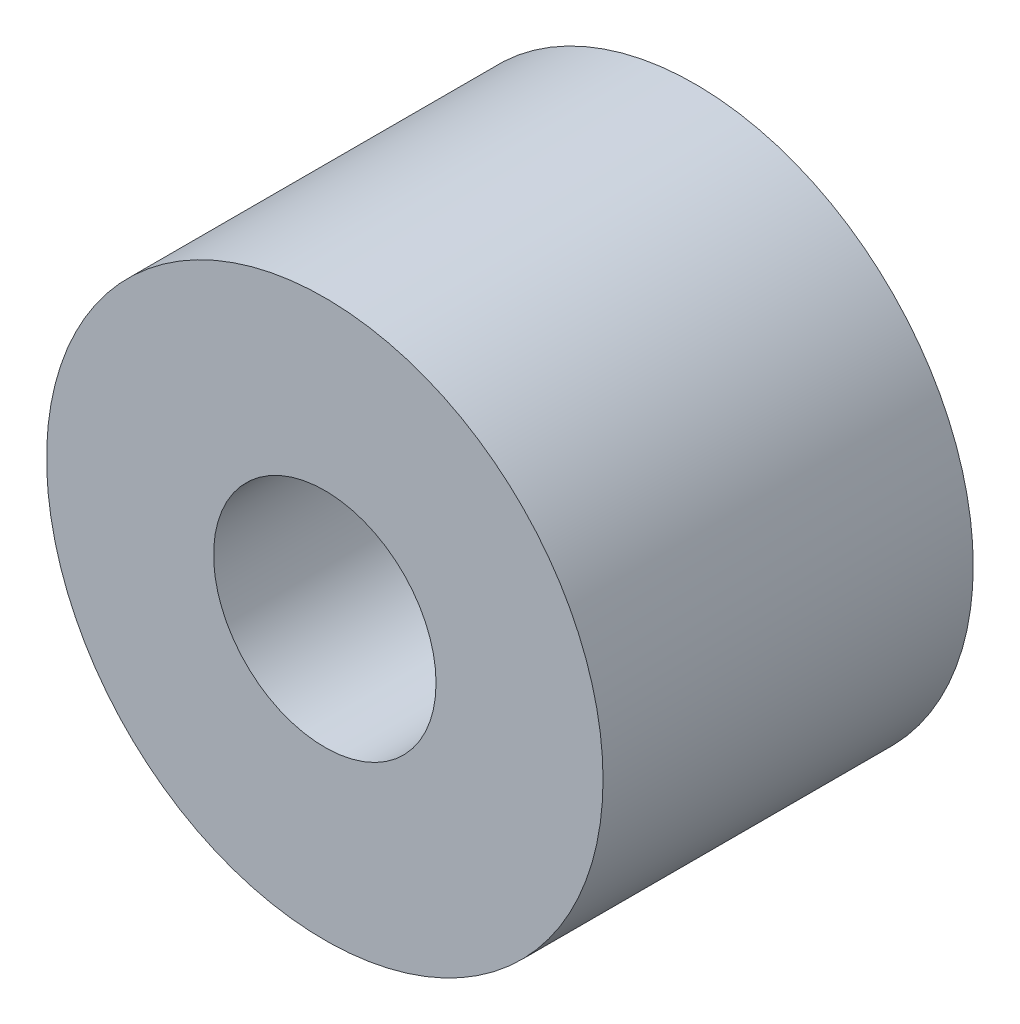
SolidWorks part; units mm, degrees
ref_plane "Płaszczyzna przednia" through (0, 0, 0) normal (0, 0, 1) x (1, 0, 0)
ref_plane "Płaszczyzna górna" through (0, 0, 0) normal (0, 1, 0) x (1, 0, 0)
ref_plane "Płaszczyzna prawa" through (0, 0, 0) normal (1, 0, 0) x (0, 0, -1)
sketch "Szkic1" plane through (0, 0, 0) normal (0, 0, 1) x (1, 0, 0)
  circle A0 centre (0, 0) radius 381
  circle A1 centre (0, 0) radius 953
  dimension "D1" = 762
  dimension "D2" = 1906
extrude "Dodanie-wyciągnięcie1" add sketch "Szkic1" along normal blind 1268
ref_axis "Oś1" through (0, 0, 1268) along (0, 0, -1)
